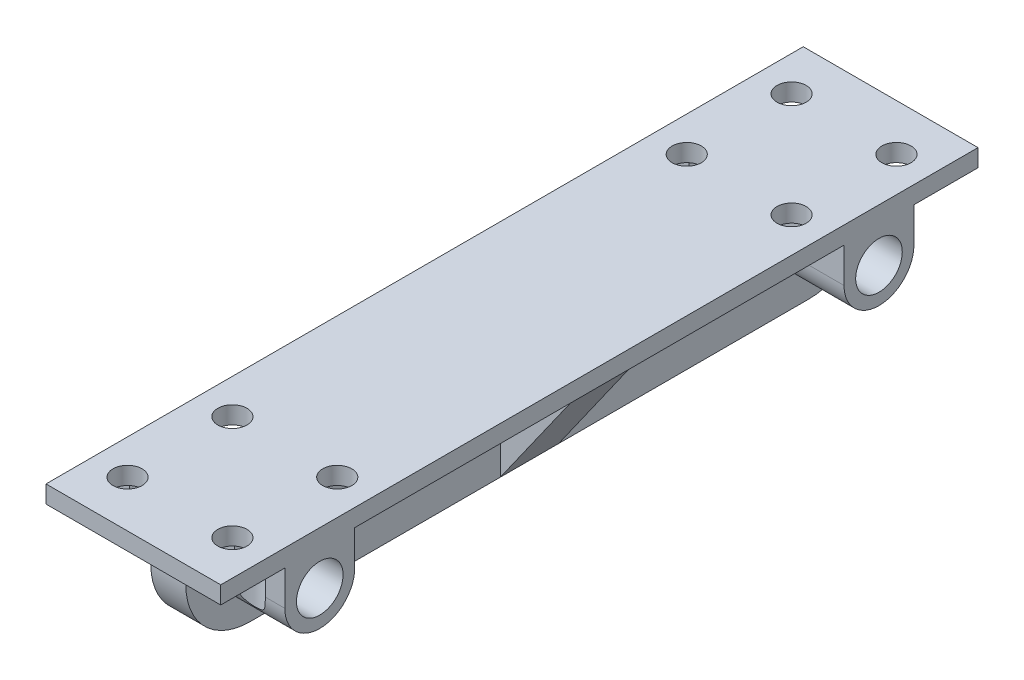
SolidWorks part; units mm, degrees
ref_plane "Front Plane" through (0, 0, 0) normal (0, 0, 1) x (1, 0, 0)
ref_plane "Top Plane" through (0, 0, 0) normal (0, 1, 0) x (1, 0, 0)
ref_plane "Right Plane" through (0, 0, 0) normal (1, 0, 0) x (0, 0, -1)
sketch "Sketch1" plane through (0, 0, 0) normal (0, 1, 0) x (1, 0, 0)
  line L1 (-22.3792, 79.995) -> (7.6208, 79.995)
  line L2 (-22.3792, 79.995) -> (-22.3792, -50.005)
  line L3 (-22.3792, -50.005) -> (7.6208, -50.005)
  line L4 (7.6208, 79.995) -> (7.6208, -50.005)
  circle A0 centre (-16.3792, -24.005) radius 2.5
  circle A1 centre (1.6208, -24.005) radius 2.5
  circle A2 centre (1.6208, -42.005) radius 2.5
  circle A3 centre (-16.3792, -42.005) radius 2.5
  circle A4 centre (-16.3792, 71.995) radius 2.5
  circle A5 centre (-16.3792, 53.995) radius 2.5
  circle A6 centre (1.6208, 71.995) radius 2.5
  circle A7 centre (1.6208, 53.995) radius 2.5
  dimension "D3" = 5
  dimension "D4" = 5
  dimension "D5" = 5
  dimension "D6" = 5
  dimension "D12" = 5
  dimension "D13" = 5
  dimension "D14" = 5
  dimension "D15" = 5
  dimension "D18" = 18
  dimension "D1" = 30
  dimension "D2" = 130
  dimension "D7" = 18
  dimension "D8" = 18
  dimension "D9" = 18
  dimension "D10" = 8
  dimension "D11" = 6
  dimension "D16" = 18
  dimension "D17" = 18
  dimension "D19" = 8
  dimension "D20" = 6
  dimension "D30" = 0
extrude "Boss-Extrude1" add sketch "Sketch1" along normal blind 3
sketch "Sketch2" plane through (0, 0, 0) normal (0, -1, 0) x (1, 0, 0)
  line L0 (-22.3792, -79.995) -> (-22.3792, 50.005) construction
  line L1 (-22.3792, -56.995) -> (7.6208, -56.995)
  line L2 (-22.3792, -56.995) -> (-22.3792, -68.995)
  line L3 (-22.3792, -68.995) -> (7.6208, -68.995)
  line L4 (7.6208, -56.995) -> (7.6208, -68.995)
  line L5 (7.6208, 50.005) -> (7.6208, -79.995) construction
  line L6 (7.6208, -79.995) -> (-22.3792, -79.995) construction
  line L7 (-22.3792, 50.005) -> (7.6208, 50.005) construction
  line L8 (-22.3792, 39.005) -> (7.6208, 39.005)
  line L9 (-22.3792, 39.005) -> (-22.3792, 27.005)
  line L10 (-22.3792, 27.005) -> (7.6208, 27.005)
  line L11 (7.6208, 39.005) -> (7.6208, 27.005)
  dimension "D1" = 12
  dimension "D2" = 11
  dimension "D3" = 12
  dimension "D4" = 11
extrude "Boss-Extrude2" add sketch "Sketch2" along normal blind 12
sketch "Sketch3" plane through (7.6208, 0, 0) normal (1, 0, 0) x (0, 0, -1)
  line L0 (-27.005, -12) -> (-27.005, 0) construction
  line L1 (-27.005, -12) -> (-39.005, -12) construction
  line L2 (56.995, -12) -> (56.995, 0) construction
  circle A0 centre (-33.005, -6) radius 4
  circle A1 centre (62.995, -6) radius 4
  dimension "D1" = 8
  dimension "D4" = 8
  dimension "D2" = 6
  dimension "D3" = 6
  dimension "D5" = 6
extrude "Cut-Extrude1" cut sketch "Sketch3" against normal up to next
fillet "Fillet1" radius 6 4 edges at (-7.3792, -12, -68.995) (-7.3792, -12, -56.995) (-7.3792, -12, 27.005) (-7.3792, -12, 39.005)
sketch "Sketch4" plane through (0, 0, 0) normal (0, -1, 0) x (1, 0, 0)
  circle A0 centre (-16.3792, -53.995) radius 4
  circle A1 centre (-16.3792, -71.995) radius 4
  circle A2 centre (1.6208, -71.995) radius 4
  circle A3 centre (1.6208, -3.995) radius 4
  circle A4 centre (1.6208, 24.005) radius 4
  circle A5 centre (-16.3792, 24.005) radius 4
  circle A6 centre (-16.3792, 42.005) radius 4
  circle A7 centre (1.6208, 42.005) radius 4
  dimension "D1" = 8
  dimension "D2" = 8
  dimension "D3" = 8
  dimension "D4" = 8
  dimension "D5" = 8
  dimension "D6" = 8
  dimension "D7" = 8
  dimension "D8" = 8
extrude "Cut-Extrude2" cut sketch "Sketch4" along normal blind 19
sketch "Sketch5" plane through (0, 0, 0) normal (0, -1, 0) x (1, 0, 0)
  line L0 (-13.7335, 27.005) -> (-1.025, 27.005) construction
  line L1 (-10.3792, 27.005) -> (-4.3792, 27.005)
  line L2 (-10.3792, 27.005) -> (-10.3792, -56.995)
  line L3 (-10.3792, -56.995) -> (-4.3792, -56.995)
  line L4 (-4.3792, 27.005) -> (-4.3792, -56.995)
  line L5 (7.6208, -56.995) -> (-13.7335, -56.995) construction
  line L6 (-13.7335, -68.995) -> (-1.025, -68.995) construction
  line L7 (-10.3792, -68.995) -> (-4.3792, -68.995)
  line L8 (-10.3792, -68.995) -> (-10.3792, -79.995)
  line L9 (-10.3792, -79.995) -> (-4.3792, -79.995)
  line L10 (-4.3792, -68.995) -> (-4.3792, -79.995)
  line L11 (7.6208, -79.995) -> (-22.3792, -79.995) construction
  line L12 (-22.3792, 50.005) -> (7.6208, 50.005) construction
  line L13 (-10.3792, 50.005) -> (-4.3792, 50.005)
  line L14 (-10.3792, 50.005) -> (-10.3792, 39.005)
  line L15 (-10.3792, 39.005) -> (-4.3792, 39.005)
  line L16 (-4.3792, 50.005) -> (-4.3792, 39.005)
  line L17 (-1.025, 39.005) -> (-13.7335, 39.005) construction
  line L18 (7.6208, 50.005) -> (7.6208, 39.005) construction
  line L20 (7.6208, 27.005) -> (7.6208, -56.995) construction
  line L21 (7.6208, -68.995) -> (7.6208, -79.995) construction
  dimension "D1" = 6
  dimension "D2" = 12
  dimension "D3" = 6
  dimension "D4" = 12
  dimension "D5" = 6
  dimension "D6" = 12
extrude "Boss-Extrude3" add sketch "Sketch5" along normal blind 6
chamfer "Chamfer1" distance 6 angle 45 2 edges at (-7.3792, -6, -79.995) (-7.3792, -6, 50.005)
sketch "Sketch6" plane through (-10.3792, 0, 0) normal (-1, 0, 0) x (0, 0, 1)
  line L0 (-62.995, -17) -> (33.005, -17)
  line L1 (-73.995, -6) -> (-68.995, -6)
  line L2 (-56.995, -6) -> (27.005, -6)
  line L3 (39.005, -6) -> (44.005, -6)
  arc A0 (-73.995, -6) -> (-62.995, -17) centre (-62.995, -6) ccw
  arc A1 (33.005, -17) -> (44.005, -6) centre (33.005, -6) ccw
  arc A2 (-68.995, -6) -> (-56.995, -6) centre (-62.995, -6) ccw
  arc A3 (27.005, -6) -> (39.005, -6) centre (33.005, -6) ccw
extrude "Boss-Extrude4" add sketch "Sketch6" against normal blind 6
sketch "Sketch7" plane through (0, 0, 0) normal (0, -1, 0) x (1, 0, 0)
  line L0 (-22.3792, -56.995) -> (-22.3792, 27.005) construction
  line L1 (-22.3792, -9.995) -> (-10.3792, -9.995)
  line L2 (-22.3792, -9.995) -> (-22.3792, -19.995)
  line L3 (-22.3792, -19.995) -> (-10.3792, -19.995)
  line L4 (-10.3792, -9.995) -> (-10.3792, -19.995)
  line L5 (-10.3792, 27.005) -> (-10.3792, -56.995) construction
  line L6 (-4.3792, -56.995) -> (-4.3792, 27.005) construction
  line L7 (-4.3792, -9.995) -> (7.6208, -9.995)
  line L8 (-4.3792, -9.995) -> (-4.3792, -19.995)
  line L9 (-4.3792, -19.995) -> (7.6208, -19.995)
  line L10 (7.6208, -9.995) -> (7.6208, -19.995)
  line L11 (7.6208, 27.005) -> (7.6208, -56.995) construction
  line L12 (-22.3792, 50.005) -> (-10.3792, 50.005) construction
  line L13 (-4.3792, 50.005) -> (7.6208, 50.005) construction
  point P16 (-16.3792, 50.005)
  dimension "D1" = 10
  dimension "D2" = 10
  dimension "D3" = 60
  dimension "D4" = 60
extrude "Boss-Extrude5" add sketch "Sketch7" along normal blind 17
chamfer "Chamfer2" distance 17 distance2 12 2 edges at (-22.3792, -17, -14.995) (7.6208, -17, -14.995) first distance on face at (-22.3792, -6, -66.995) first distance on face at (7.6208, -6, -66.995)
